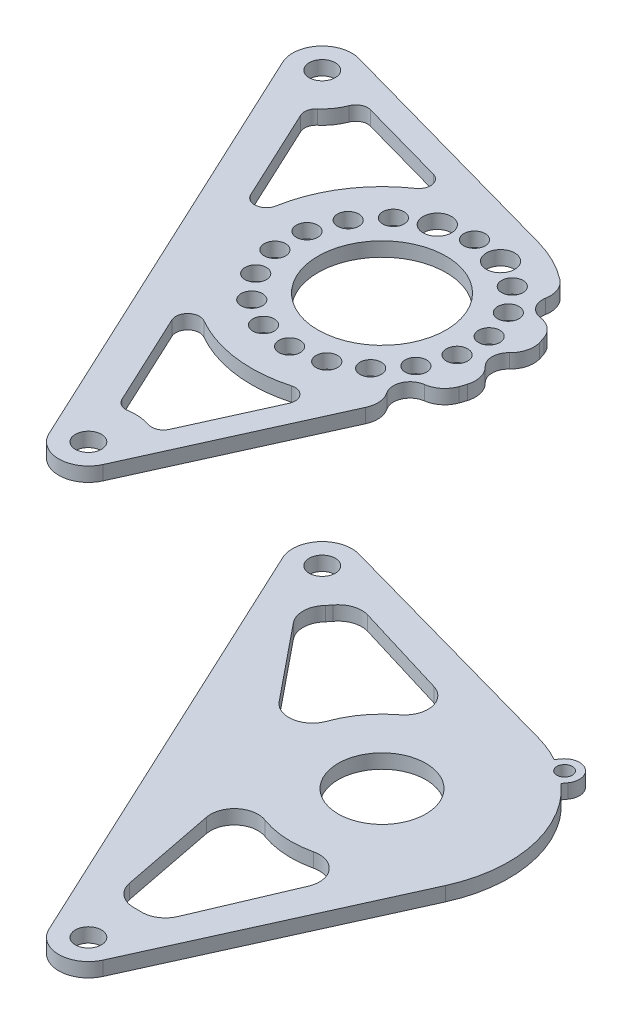
SolidWorks part; units mm, degrees
note: '?' marks a value the reader was unsure of.
material "6061-T6 (SS)"
ref_plane "Front Plane" through (0, 0, 0) normal (0, 0, 1) x (1, 0, 0)
ref_plane "Top Plane" through (0, 0, 0) normal (0, 1, 0) x (1, 0, 0)
ref_plane "Right Plane" through (0, 0, 0) normal (1, 0, 0) x (0, 0, -1)
sketch "Sketch1" plane through (0, 0, 0) normal (0, 1, 0) x (1, 0, 0)
  line L0 (43.1017, -16.07) -> (4.1217, -120.6193)
  line L1 (-18.9163, -121.5423) -> (-105.3458, 63.5028)
  line L2 (-89.8517, 80.5771) -> (15.3404, 43.3667)
  line L3 (-125.5219, 78.2652) -> (-20.5452, -146.4892) construction
  line L4 (2.1058, -135.9095) -> (-102.8708, 88.8449) construction
  line L5 (-114.1964, 83.555) -> (-9.2197, -141.1993) construction
  line L6 (0, 0) -> (-114.1964, 83.555) construction
  line L7 (-9.2197, -141.1993) -> (0, 0) construction
  arc A0 (43.1017, -16.07) -> (15.3404, 43.3667) centre (0, 0) ccw
  arc A1 (4.1217, -120.6193) -> (-18.9163, -121.5423) centre (-7.5908, -116.2524) cw
  arc A2 (-105.3458, 63.5028) -> (-89.8517, 80.5771) centre (-94.0203, 68.7927) cw
  circle A3 centre (0, 0) radius 39 construction
  circle A4 centre (0, 0) radius 27
  circle A5 centre (-7.5908, -116.2524) radius 5.5
  circle A6 centre (-94.0203, 68.7927) radius 5.5
  circle A7 centre (-114.1964, 83.555) radius 12.5 construction
  circle A8 centre (-9.2197, -141.1993) radius 12.5 construction
  dimension "D1" = 78
  dimension "D2" = 54
  dimension "D3" = 46
  dimension "D4" = 12.5
  dimension "D5" = 11
  dimension "D6" = 12.5
  dimension "D7" = 11
  dimension "D8" = 25
  dimension "D9" = 25
extrude "Boss-Extrude1" add sketch "Sketch1" along normal blind 6
sketch "Sketch8" plane through (0, 0, 0) normal (0, 1, 0) x (1, 0, 0)
  circle A0 centre (0, 0) radius 104 construction
  dimension "D1" = 208
sketch "Sketch7" plane through (0, 6, 0) normal (0, 1, 0) x (1, 0, 0)
  circle A0 centre (0, 0) radius 53.5 construction
  circle A1 centre (43.2871, 31.44) radius 7.06
  circle A2 centre (53.5, 0) radius 7.06
  circle A3 centre (43.2871, -31.44) radius 7.06
  point P5 (43.2871, 38.5)
  dimension "D1" = 107
  dimension "D2" = 31.44
  dimension "D3" = 38.5
ref_axis "Axis1" through (0, 71.351, 0) along (0, -1, 0)?
hole_wizard "M8 Clearance Hole1" positions "Sketch2" profile "Sketch3" hole size "M8" standard "ANSI Metric"
sketch "Sketch2" plane through (0, 6, 0) normal (0, 1, 0) x (1, 0, 0)
  point P0 (0, 39)
  point P71 (13.3388, 36.648) [skipped]
  point P72 (25.0687, 29.8757)
  point P73 (33.775, 19.5)
  point P74 (38.4075, 6.7723)
  point P75 (38.4075, -6.7723)
  point P76 (33.775, -19.5)
  point P77 (25.0687, -29.8757)
  point P78 (13.3388, -36.648)
  point P79 (0, -39)
  point P80 (-13.3388, -36.648)
  point P81 (-25.0687, -29.8757)
  point P82 (-33.775, -19.5)
  point P83 (-38.4075, -6.7723)
  point P84 (-38.4075, 6.7723)
  point P85 (-33.775, 19.5)
  point P86 (-25.0687, 29.8757)
  point P87 (-13.3388, 36.648) [skipped]
  dimension "D2" = 39
  dimension "D1" = 18
sketch "Sketch3" plane through (0, 6, -39) normal (1, 0, 0) x (0, 0, 1)
  line L0 (0, 0) -> (0, 6)
  line L1 (0, 6) -> (4.5, 6)
  line L2 (4.5, 6) -> (4.5, 0)
  line L5 (4.5, 0) -> (0, 0)
  line L11 (0, -6.35) -> (0, 107.95) construction
  dimension "Thru Hole Dia." = 9
  dimension "Thru Hole Depth" = 6
sketch "Sketch4" plane through (0, 6, 0) normal (0, 1, 0) x (1, 0, 0)
  line L3 (0, -94.6) -> (0, 94.6) construction
  circle A0 centre (-13.335, 36.6494) radius 6
  circle A1 centre (0, 0) radius 39 construction
  circle A8 centre (13.335, 36.6494) radius 6
  dimension "D1" = 12
  dimension "D3" = 26.67
extrude "Cut-Extrude1" cut sketch "Sketch4" against normal through all contours A0 | A8
ref_plane "Plane1" through (0, -175, 0) normal (0, 1, 0) x (1, 0, 0)
sketch "Sketch13" plane through (0, 0, 0) normal (0, -1, 0) x (1, 0, 0)
  line L0 (48.7442, 22.0512) -> (3.7981, 121.4046)
  line L1 (14.3752, -51.5325) -> (-90.6616, -80.833)
  line L2 (15.3404, -43.3667) -> (-90.6616, -80.833)
  line L3 (43.1017, 16.07) -> (3.7981, 121.4046)
  arc A0 (14.3752, -51.5325) -> (48.7442, 22.0512) centre (0, 0) ccw
  arc A1 (4.1217, 120.6193) -> (-18.9163, 121.5423) centre (-7.5908, 116.2524) ccw construction
  arc A2 (-105.3458, -63.5028) -> (-89.8517, -80.5771) centre (-94.0203, -68.7927) ccw construction
  arc A3 (43.1017, 16.07) -> (15.3404, -43.3667) centre (0, 0) cw
extrude "Boss-Extrude3" add sketch "Sketch13" against normal up to surface (6 mm away) contours L3 L0 A0 L1 L2 A3 up to face at (13.335, 6, -30.6494)
sketch "Sketch9" plane through (0, -175, 0) normal (0, 1, 0) x (1, 0, 0)
  line L0 (-90.6616, 80.833) -> (14.3752, 51.5325)
  line L1 (48.7442, -22.0512) -> (3.7981, -121.4046)
  line L2 (-18.9163, -121.5423) -> (-105.3458, 63.5028)
  line L3 (14.3752, 51.5325) -> (-90.6616, 80.833) construction
  arc A0 (14.3752, 51.5325) -> (48.7442, -22.0512) centre (0, 0) cw
  arc A1 (3.7981, -121.4046) -> (-18.9163, -121.5423) centre (-7.5908, -116.2524) cw
  arc A2 (-105.3458, 63.5028) -> (-90.6616, 80.833) centre (-94.0203, 68.7927) cw
  circle A3 centre (0, 0) radius 18.5
  circle A5 centre (-94.0203, 68.7927) radius 5.5
  circle A6 centre (-7.5908, -116.2524) radius 5.5
  arc A7 (48.7442, -22.0512) -> (14.3752, 51.5325) centre (0, 0) ccw construction
  circle A8 centre (-7.5908, -116.2524) radius 5.5 construction
  circle A10 centre (-94.0203, 68.7927) radius 5.5 construction
  dimension "D1" = 37
extrude "Boss-Extrude2" add sketch "Sketch9" against normal blind 6 separate body
extrude "Cut-Extrude4" cut sketch "Sketch7" against normal up to surface (6 mm away) up to face at (-22.767, 0, 10.6339)
fillet "Fillet1" radius 10 6 edges at (47.0501, 3, -25.4664) (38.7704, 3, -36.8661) (53.0342, 3, 7.0446) (53.0342, 3, -7.0446) (47.1656, 3, 25.5407) (41.417, 3, 38.2478)
sketch "Sketch14" plane through (0, 6, 0) normal (0, 1, 0) x (1, 0, 0)
  line L0 (-83.8649, 51.5628) -> (-53.117, -14.2684)
  line L1 (-74.2352, 65.869) -> (-20.7304, 50.9436)
  line L2 (-18.9163, -121.5423) -> (-105.3458, 63.5028) construction
  line L3 (14.3752, 51.5325) -> (-90.6616, 80.833) construction
  line L4 (38.2918, -45.1562) -> (3.7981, -121.4046) construction
  line L5 (-42.0669, 56.8955) -> (-39.38, 66.5278) construction
  line L6 (25.7609, -48.594) -> (2.8658, -99.2037)
  line L7 (-14.2855, -97.4062) -> (-45.0335, -31.575)
  line L9 (12.5623, -77.7695) -> (21.6734, -81.8912)
  line L10 (38.2918, -45.1562) -> (3.7981, -121.4046) construction
  line L11 (-61.708, -28.8221) -> (0, 0) construction
  line L12 (-114.1964, 83.555) -> (-9.2197, -141.1993) construction
  line L13 (-53.117, -14.2684) -> (0, 0) construction
  line L14 (-45.0335, -31.575) -> (0, 0) construction
  arc A0 (-20.7304, 50.9436) -> (-53.117, -14.2684) centre (0, 0) ccw
  arc A1 (-74.2352, 65.869) -> (-83.8649, 51.5628) centre (-94.0203, 68.7927) cw
  arc A2 (-45.0335, -31.575) -> (25.7609, -48.594) centre (0, 0) ccw
  arc A3 (-14.2855, -97.4062) -> (2.8658, -99.2037) centre (-7.5908, -116.2524) cw
  dimension "D2" = 55
  dimension "D3" = 20
  dimension "D1" = 10
  dimension "D5" = 10
  dimension "D6" = 10
extrude "Cut-Extrude5" cut sketch "Sketch14" against normal up to surface (6 mm away) contours L1 A1 L0 A0 | L7 A3 L6 A2 up to face at (19.3286, 0, 3.147)
fillet "Fillet2" radius 5 8 edges at (25.7609, 3, 48.594) (-45.0335, 3, 31.575) (2.8658, 3, 99.2037) (-14.2855, 3, 97.4062) (-53.117, 3, 14.2684) (-20.7304, 3, -50.9436) (-74.2352, 3, -65.869) (-83.8649, 3, -51.5628)
sketch "Sketch15" plane through (0, -181, 0) normal (0, -1, 0) x (1, 0, 0)
  line L0 (0, 0) -> (-62.1311, 29.0197) construction
  line L1 (11.1886, -36.8384) -> (-74.4051, -62.8351)
  line L2 (-85.8484, -49.9919) -> (-37.1819, 9.9879)
  line L3 (35.4307, 15.0637) -> (0.4302, 97.3867)
  line L4 (-31.5235, 22.1025) -> (-16.7632, 97.919)
  line L5 (-18.9163, 121.5423) -> (-105.3458, -63.5028) construction
  line L6 (-31.5235, 22.1025) -> (0, 0) construction
  line L7 (-37.1819, 9.9879) -> (0, 0) construction
  arc A0 (11.1886, -36.8384) -> (-37.1819, 9.9879) centre (0, 0) cw
  arc A1 (-74.4051, -62.8351) -> (-85.8484, -49.9919) centre (-94.0203, -68.7927) ccw
  circle A2 centre (-94.0203, -68.7927) radius 5.5 construction
  circle A4 centre (0, 0) radius 18.5 construction
  arc A5 (35.4307, 15.0637) -> (-31.5235, 22.1025) centre (0, 0) ccw
  arc A6 (0.4302, 97.3867) -> (-16.7632, 97.919) centre (-7.5908, 116.2524) cw
  circle A7 centre (-7.5908, 116.2524) radius 5.5 construction
  dimension "D1" = 15
  dimension "D4" = 20
  dimension "D2" = 10
  dimension "D3" = 10
extrude "Cut-Extrude6" cut sketch "Sketch15" against normal up to surface (6 mm away) up to face at (-7.5908, -175, 121.7524)
fillet "Fillet3" radius 10 8 edges at (-37.1819, -178, 9.9879) (-85.8484, -178, -49.9919) (-74.4051, -178, -62.8351) (11.1886, -178, -36.8384) (0.4302, -178, 97.3867) (-16.7632, -178, 97.919) (-31.5235, -178, 22.1025) (35.4307, -178, 15.0637)
sketch "Sketch17" plane through (0, -181, 0) normal (0, -1, 0) x (1, 0, 0)
  line L0 (32, 0) -> (32, -45) construction
  line L1 (37.0935, -41.378) -> (35.8857, -39.6795)
  line L2 (26.9065, -48.622) -> (25.6988, -46.9236)
  line L3 (35.8857, -39.6795) -> (25.6988, -46.9236) construction
  circle A0 centre (0, 0) radius 32 construction
  circle A1 centre (32, -45) radius 3.25 construction
  arc A2 (37.0935, -41.378) -> (26.9065, -48.622) centre (32, -45) cw
  circle A3 centre (0, 0) radius 53.5 construction
  arc A4 (25.6988, -46.9236) -> (35.8857, -39.6795) centre (0, 0) ccw
  dimension "D1" = 64
  dimension "D3" = 6.5
  dimension "D4" = 3
  dimension "D2" = 45
extrude "Boss-Extrude4" add sketch "Sketch17" against normal up to surface (6 mm away) up to face at (-54.9245, -175, -39.3314)
sketch "Sketch19" plane through (0, -181, 0) normal (0, -1, 0) x (1, 0, 0)
  circle A0 centre (32, -45) radius 3.25
extrude "Cut-Extrude7" cut sketch "Sketch19" against normal up to next (6 mm away)
